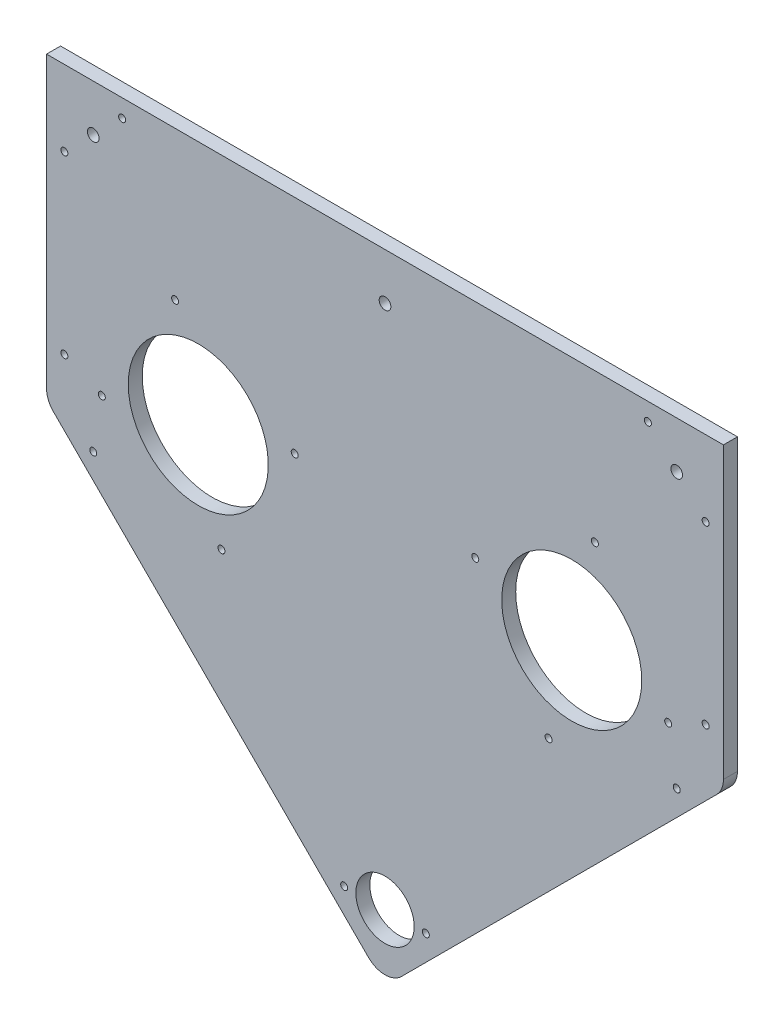
SolidWorks part; units mm, degrees
ref_plane "Front Plane" through (0, 0, 0) normal (0, 0, 1) x (1, 0, 0)
ref_plane "Top Plane" through (0, 0, 0) normal (0, 1, 0) x (1, 0, 0)
ref_plane "Right Plane" through (0, 0, 0) normal (1, 0, 0) x (0, 0, -1)
sketch "Sketch1" plane through (0, 0, 0) normal (0, 0, 1) x (1, 0, 0)
  line L0 (-125, 100) -> (125, 100) construction
  line L1 (-125, 0) -> (125, 0) construction
  line L2 (-137.3744, 87.6256) -> (-125, 100) construction
  line L3 (0, -125) -> (-125, 0) construction
  line L4 (0, -125) -> (-17.5, -125) construction
  line L5 (-125, -17.5) -> (-125, 0) construction
  line L6 (0, -125) -> (0, 100) construction
  line L7 (-145, 120) -> (145, 120)
  line L8 (145, 120) -> (145, -8.2843)
  line L9 (145, -8.2843) -> (0, -153.2843)
  line L10 (0, -153.2843) -> (-145, -8.2843)
  line L11 (-145, -8.2843) -> (-145, 120)
  circle A0 centre (-125, 100) radius 12.5 construction
  circle A1 centre (125, 100) radius 12.5 construction
  circle A4 centre (0, -125) radius 12.5
  circle A5 centre (-137.3744, 87.6256) radius 1.5
  circle A6 centre (-112.6256, 112.3744) radius 1.5
  circle A7 centre (-137.3744, 12.3744) radius 1.5
  circle A8 centre (-125, -17.5) radius 1.5
  circle A9 centre (-17.5, -125) radius 1.5
  circle A10 centre (-125, 0) radius 12.5 construction
  circle A11 centre (125, 0) radius 12.5 construction
  circle A12 centre (-125, 0) radius 17.5 construction
  circle A13 centre (-125, 100) radius 17.5 construction
  circle A14 centre (0, -125) radius 17.5 construction
  circle A15 centre (17.5, -125) radius 1.5
  circle A16 centre (125, -17.5) radius 1.5
  circle A17 centre (137.3744, 12.3744) radius 1.5
  circle A18 centre (137.3744, 87.6256) radius 1.5
  circle A19 centre (112.6256, 112.3744) radius 1.5
  circle A20 centre (0, 100) radius 2.5
  circle A21 centre (-125, 100) radius 2.5
  circle A22 centre (125, 100) radius 2.5
  point P12 (0, 100)
  point P45 (0, 120)
  dimension "D1" = 25
  dimension "D5" = 3
  dimension "D2" = 5
  dimension "D4" = 100
  dimension "D6" = 5
  dimension "D7" = 135
  dimension "D8" = 45
  dimension "D9" = 250
  dimension "D10" = 45
  dimension "D11" = 20
  dimension "D12" = 20
  dimension "D13" = 20
  dimension "D14" = 20
  dimension "D15" = 20
  dimension "D3" = 125
extrude "Boss-Extrude1" add sketch "Sketch1" along normal blind 6
fillet "Fillet1" radius 10 3 edges at (-145, -8.2843, 3) (145, -8.2843, 3) (0, -153.2843, 3)
sketch "Sketch2" plane through (0, 0, 6) normal (0, 0, 1) x (1, 0, 0)
  line L0 (121.326, 5.0796) -> (38.674, 24.9204) construction
  line L1 (70.0796, -26.326) -> (89.9204, 56.326) construction
  line L2 (0, 0) -> (0, 100) construction
  line L3 (145, 120) -> (-145, 120) construction
  line L4 (-145, 120) -> (-145, -4.1421) construction
  circle A0 centre (80, 15) radius 42.5 construction
  circle A1 centre (38.674, 24.9204) radius 1.5
  circle A2 centre (89.9204, 56.326) radius 1.5
  circle A3 centre (121.326, 5.0796) radius 1.5
  circle A4 centre (70.0796, -26.326) radius 1.5
  circle A5 centre (80, 15) radius 30
  circle A6 centre (-38.674, 24.9204) radius 1.5
  circle A7 centre (-89.9204, 56.326) radius 1.5
  circle A8 centre (-70.0796, -26.326) radius 1.5
  circle A9 centre (-121.326, 5.0796) radius 1.5
  circle A10 centre (-80, 15) radius 42.5 construction
  circle A11 centre (-80, 15) radius 30
  circle A12 centre (-80, 15) radius 47.5 construction
  circle A13 centre (-137.3744, 12.3744) radius 3 construction
  circle A14 centre (-125, -17.5) radius 3 construction
  point P6 (80, 15)
  point P27 (-80, 15)
  dimension "D1" = 85
  dimension "D2" = 3
  dimension "D3" = 60
  dimension "D4" = 95
  dimension "D5" = 6
  dimension "D6" = 105
  dimension "D7" = 65
extrude "Cut-Extrude1" cut sketch "Sketch2" against normal blind 10
equation "\"D1@Sketch1\" = \"cf_tube_outer_diameter\""
equation "\"D9@Sketch1\"= \"mid_plate_horizontal_spacing\""
equation "\"mid_plate_mid_to_top\" = 100mm"
equation "\"mid_plate_mid_to_bottom\" = 125mm"
equation "\"mid_plate_horizontal_spacing\" = 250mm"
equation "\"cf_tube_outer_diameter\" = 25mm"
equation "\"D4@Sketch1\"=\"mid_plate_mid_to_top\""
equation "\"D3@Sketch1\"=\"mid_plate_mid_to_bottom\""
